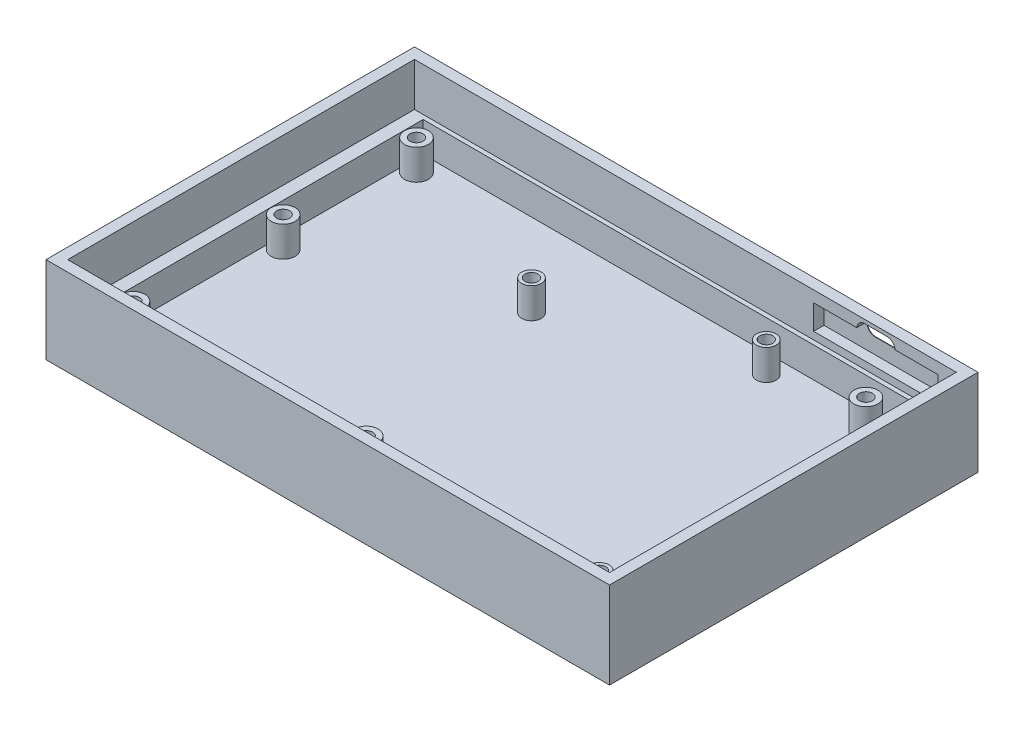
SolidWorks part; units mm, degrees
ref_plane "Front Plane" through (0, 0, 0) normal (0, 0, 1) x (1, 0, 0)
ref_plane "Top Plane" through (0, 0, 0) normal (0, 1, 0) x (1, 0, 0)
ref_plane "Right Plane" through (0, 0, 0) normal (1, 0, 0) x (0, 0, -1)
sketch "Sketch1" plane through (0, 0, 0) normal (0, 1, 0) x (1, 0, 0)
  line L0 (-65, 42.5) -> (65, 42.5)
  line L1 (-62.5, 40) -> (62.5, 40)
  line L2 (-62.5, 40) -> (-62.5, -40)
  line L3 (-62.5, -40) -> (62.5, -40)
  line L4 (62.5, 40) -> (62.5, -40)
  line L5 (-62.5, 40) -> (62.5, -40) construction
  line L6 (-62.5, -40) -> (62.5, 40) construction
  line L7 (65, 42.5) -> (65, -42.5)
  line L8 (-65, -42.5) -> (65, -42.5)
  line L9 (-65, 42.5) -> (-65, -42.5)
  point P0 (0, 0)
  dimension "D1" = 125
  dimension "D2" = 80
  dimension "D3" = 2.5
extrude "Boss-Extrude1" add sketch "Sketch1" along normal blind 3 contours L2 L1 L4 L3
extrude "Boss-Extrude2" add sketch "Sketch1<3>" along normal blind 20
sketch "Sketch1<3>" plane through (0, 0, 0) normal (0, 1, 0) x (1, 0, 0) same geometry as "Sketch1"
sketch "Sketch2" plane through (0, 0, 0) normal (0, 1, 0) x (1, 0, 0)
  line L1 (-62.5, -40) -> (62.5, -40)
  line L2 (-62.5, -40) -> (-62.5, 40)
  line L3 (-62.5, 40) -> (62.5, 40)
  line L4 (62.5, -40) -> (62.5, 40)
  line L9 (-59.5, 39) -> (60.5, 39)
  line L10 (-59.5, 39) -> (-59.5, -37)
  line L11 (-59.5, -37) -> (60.5, -37)
  line L12 (60.5, 39) -> (60.5, -37)
  point P0 (0, 0)
  point P9 (0, 0)
  dimension "D1" = 3
  dimension "D2" = 2
  dimension "D3" = 1
  dimension "D4" = 3
extrude "Boss-Extrude3" add sketch "Sketch2" along normal blind 10
sketch "Sketch3" plane through (0, 0, -40) normal (0, 0, -1) x (-1, 0, 0)
  line L1 (-58.2575, 17.4158) -> (-29.5791, 17.4158)
  line L2 (-58.2575, 17.4158) -> (-58.2575, 11.717)
  line L3 (-58.2575, 11.717) -> (-29.5791, 11.717)
  line L4 (-29.5791, 17.4158) -> (-29.5791, 11.717)
extrude "Cut-Extrude1" cut sketch "Sketch3" along normal blind 2.4
sketch "Sketch4" plane through (0, 0, -42.5) normal (0, 0, -1) x (-1, 0, 0)
  line L0 (-46.4794, 17.2233) -> (-41.4272, 17.2233) construction
  line L1 (-46.4794, 19.1497) -> (-41.4272, 19.1497)
  line L2 (-46.4794, 15.2968) -> (-41.4272, 15.2968)
  arc A0 (-46.4794, 19.1497) -> (-46.4794, 15.2968) centre (-46.4794, 17.2233) ccw
  arc A1 (-41.4272, 15.2968) -> (-41.4272, 19.1497) centre (-41.4272, 17.2233) ccw
  point P2 (-43.9533, 17.2233)
extrude "Cut-Extrude2" cut sketch "Sketch4" against normal blind 3
sketch "Sketch5" plane through (0, 3, 0) normal (0, 1, 0) x (1, 0, 0)
  line L0 (-56.6664, -30.7729) -> (50.9406, -30.7729) construction
  line L1 (-56.6664, 34.6235) -> (-56.6664, -30.7729) construction
  circle A0 centre (-56.6664, -30.7729) radius 2.75
  circle A1 centre (-56.6664, 34.6235) radius 2.75
  circle A2 centre (-56.6664, 3.8749) radius 2.75
  circle A3 centre (-15.3764, 19.8794) radius 2.2593
  circle A4 centre (24.0416, 34.6235) radius 2.2593
  circle A5 centre (50.9406, -30.7729) radius 2.2593
  circle A6 centre (-2.8629, -30.7729) radius 2.75
  circle A7 centre (47.0168, 34.6235) radius 2.75
  circle A8 centre (-56.6664, 34.6235) radius 1.5
  circle A9 centre (-15.3764, 19.8794) radius 1.5
  circle A10 centre (24.0416, 34.6235) radius 1.5
  circle A11 centre (47.0168, 34.6235) radius 1.5
  circle A12 centre (-2.8629, -30.7729) radius 1.5
  circle A13 centre (50.9406, -30.7729) radius 1.5
  circle A14 centre (-56.6664, -30.7729) radius 1.5
  circle A15 centre (-56.6664, 3.8749) radius 1.5
  dimension "D1" = 5.5
  dimension "D2" = 3
extrude "Boss-Extrude4" add sketch "Sketch5" along normal blind 7
